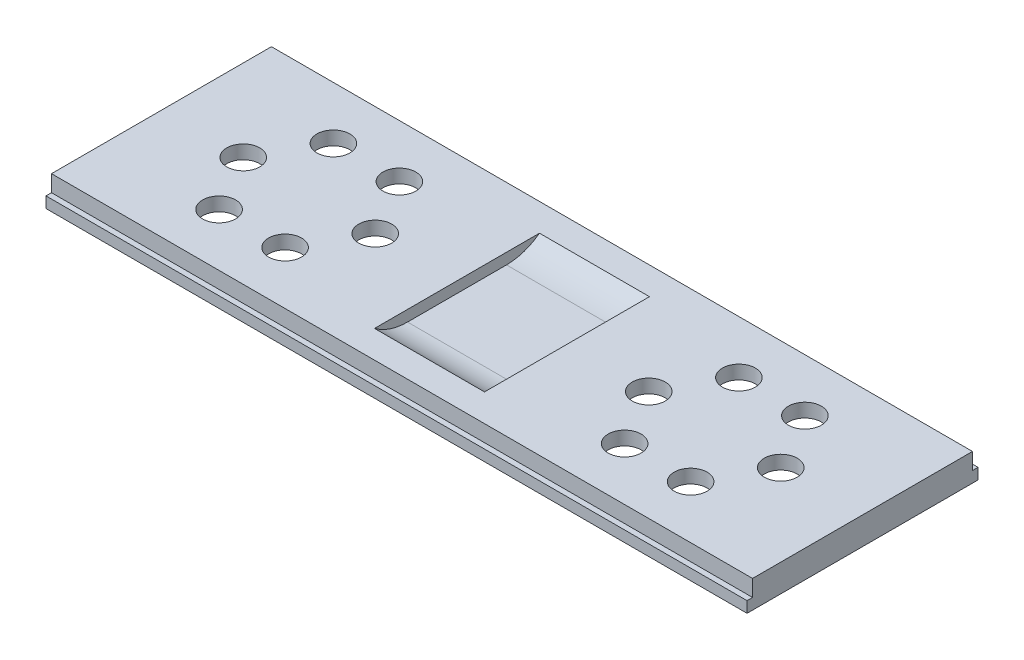
SolidWorks part; units mm, degrees
ref_plane "Front Plane" through (0, 0, 0) normal (0, 0, 1) x (1, 0, 0)
ref_plane "Top Plane" through (0, 0, 0) normal (0, 1, 0) x (1, 0, 0)
ref_plane "Right Plane" through (0, 0, 0) normal (1, 0, 0) x (0, 0, -1)
sketch "Sketch1" plane through (0, 0, 0) normal (0, 1, 0) x (1, 0, 0)
  line L1 (-51.2673, 18.3939) -> (76.2327, 18.3939)
  line L2 (-51.2673, 18.3939) -> (-51.2673, -23.6061)
  line L3 (-51.2673, -23.6061) -> (76.2327, -23.6061)
  line L4 (76.2327, 18.3939) -> (76.2327, -23.6061)
extrude "Boss-Extrude1" add sketch "Sketch1" along normal blind 5
sketch "Sketch2" plane through (0, 5, 0) normal (0, 1, 0) x (1, 0, 0)
  line L0 (-51.2673, 18.3939) -> (-51.2673, -23.6061) construction
  line L1 (76.2327, 18.3939) -> (-51.2673, 18.3939)
  line L2 (76.2327, 18.3939) -> (76.2327, 17.3939)
  line L3 (76.2327, 17.3939) -> (-51.2673, 17.3939)
  line L4 (-51.2673, 18.3939) -> (-51.2673, 17.3939)
  line L6 (76.2327, -23.6061) -> (-51.2673, -23.6061)
  line L7 (76.2327, -23.6061) -> (76.2327, -22.6061)
  line L8 (76.2327, -22.6061) -> (-51.2673, -22.6061)
  line L9 (-51.2673, -23.6061) -> (-51.2673, -22.6061)
extrude "Cut-Extrude1" cut sketch "Sketch2" against normal blind 3
sketch "Sketch4" plane through (0, 5, 0) normal (0, 1, 0) x (1, 0, 0)
  line L0 (-51.2673, 17.3939) -> (76.2327, -22.6061)
  line L1 (76.2327, 17.3939) -> (-51.2673, -22.6061)
  point P8 (12.4827, -2.6061)
sketch "Sketch7" plane through (0, 5, 0) normal (0, 1, 0) x (1, 0, 0)
  line L1 (2.4827, 12.3939) -> (22.4827, 12.3939)
  line L2 (2.4827, 12.3939) -> (2.4827, -17.6061)
  line L3 (2.4827, -17.6061) -> (22.4827, -17.6061)
  line L4 (22.4827, 12.3939) -> (22.4827, -17.6061)
  line L5 (2.4827, 12.3939) -> (22.4827, -17.6061) construction
  line L6 (2.4827, -17.6061) -> (22.4827, 12.3939) construction
  point P0 (12.4827, -2.6061)
extrude "Cut-Extrude5" cut sketch "Sketch7" against normal blind 2
shell "Shell8" thickness 2.5 removed face at (12.4827, 0, 2.6061)
fillet "Fillet3" radius 10 1 edges at (12.4827, 3, 17.6061)
fillet "Fillet4" radius 10 1 edges at (12.4827, 3, -12.3939)
sketch "Sketch8" plane through (0, 5, 0) normal (0, 1, 0) x (1, 0, 0)
  line L0 (22.4827, -17.6061) -> (-51.2673, -17.6061)
  line L1 (-51.2673, 17.3939) -> (-51.2673, -22.6061) construction
  line L2 (-51.2673, -17.6061) -> (76.2327, -17.6061)
  line L3 (76.2327, -22.6061) -> (76.2327, 17.3939) construction
  line L4 (2.4827, 12.3939) -> (76.2327, 12.3939)
  line L5 (76.2327, 12.3939) -> (-51.2673, 12.3939)
  line L6 (-51.2673, -17.6061) -> (2.4827, 12.3939)
  line L7 (-51.2673, 12.3939) -> (2.4827, -17.6061)
  line L8 (22.4827, -17.6061) -> (76.2327, 12.3939)
  line L9 (22.4827, 12.3939) -> (76.2327, -17.6061)
  circle A0 centre (-24.3923, -2.6061) radius 12
  circle A1 centre (49.3577, -2.6061) radius 12
  point P20 (-12.3923, -2.6061)
  point P21 (61.3577, -2.6061)
sketch "Sketch10" plane through (0, 5, 0) normal (0, 1, 0) x (1, 0, 0)
  circle A0 centre (-12.3923, -2.6061) radius 3
  circle A1 centre (-18.3923, -12.9984) radius 3
  circle A2 centre (-30.3923, -12.9984) radius 3
  circle A3 centre (-36.3923, -2.6061) radius 3
  circle A4 centre (-30.3923, 7.7862) radius 3
  circle A5 centre (-18.3923, 7.7862) radius 3
  circle A6 centre (61.3577, -2.6061) radius 3
  circle A7 centre (55.3577, -12.9984) radius 3
  circle A8 centre (43.3577, -12.9984) radius 3
  circle A9 centre (37.3577, -2.6061) radius 3
  circle A10 centre (43.3577, 7.7862) radius 3
  circle A11 centre (55.3577, 7.7862) radius 3
  point P16 (-24.3923, -2.6061)
  point P30 (49.3577, -2.6061)
  dimension "D1" = 6
  dimension "D2" = 6
extrude "Cut-Extrude6" cut sketch "Sketch10" against normal blind 2.5
